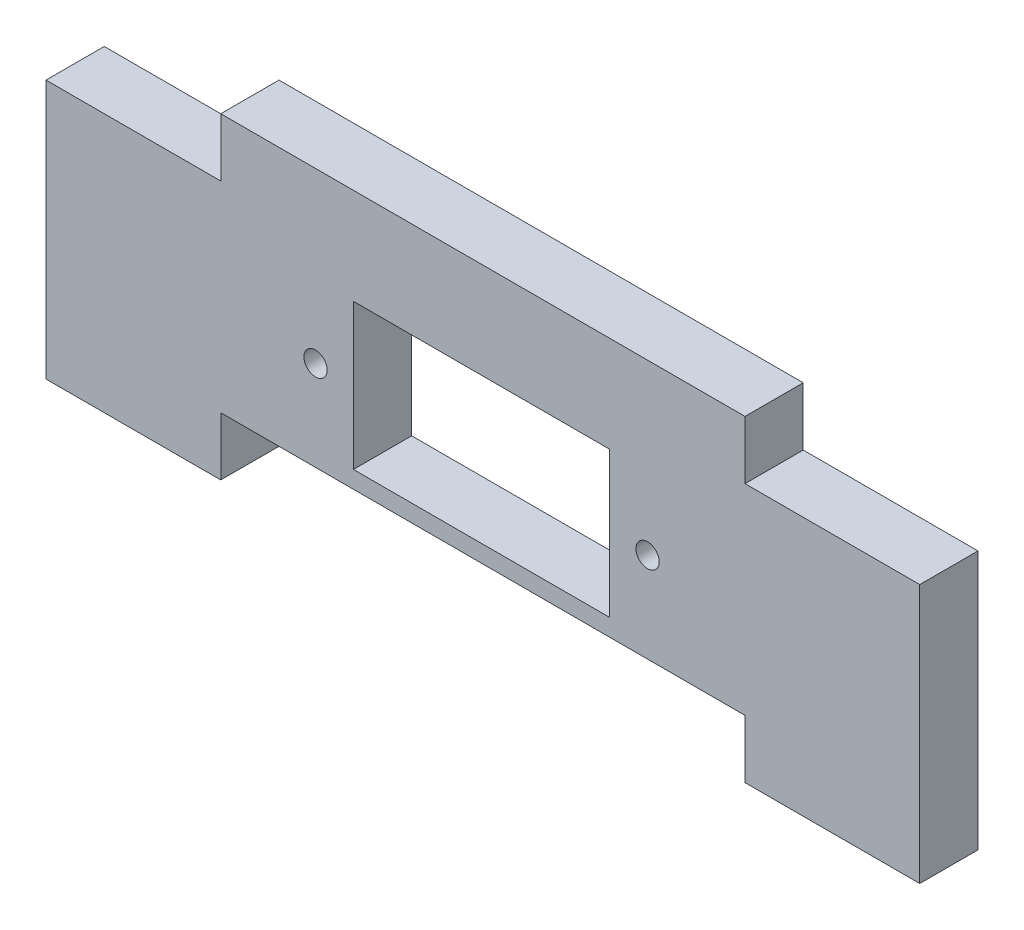
SolidWorks part; units mm, degrees
ref_plane "Front Plane" through (0, 0, 0) normal (0, 0, 1) x (1, 0, 0)
ref_plane "Top Plane" through (0, 0, 0) normal (0, 1, 0) x (1, 0, 0)
ref_plane "Right Plane" through (0, 0, 0) normal (1, 0, 0) x (0, 0, -1)
sketch "Sketch1" plane through (0, 0, 232.248) normal (0, 0, 1) x (1, 0, 0)
  line L0 (-82.2575, 116.9148) -> (-82.2575, 82.4648)
  line L1 (-82.2575, 82.4648) -> (-82.2575, 72.4648)
  line L2 (-29.4825, 110.4148) -> (14.5175, 110.4148)
  line L3 (-82.2575, 72.4648) -> (-52.2575, 72.4648)
  line L4 (-29.4825, 82.4648) -> (14.9675, 82.4648)
  line L5 (-52.2575, 72.4648) -> (-52.2575, 82.4648)
  line L6 (-29.4825, 85.4148) -> (14.5175, 85.4148)
  line L7 (-52.2575, 82.4648) -> (-29.4825, 82.4648)
  line L8 (-29.4825, 85.4148) -> (-29.4825, 110.4148)
  line L9 (-52.2575, 126.9148) -> (37.7425, 126.9148)
  line L11 (280.006, 122.4648) -> (-294.5209, 122.4648) construction
  line L12 (-29.4825, 116.9148) -> (14.9675, 116.9148) construction
  line L13 (-52.2575, 126.9148) -> (-52.2575, 116.9148)
  line L14 (-52.2575, 116.9148) -> (-82.2575, 116.9148)
  line L15 (37.7425, 82.4648) -> (14.9675, 82.4648)
  line L16 (-7.2575, 111.3889) -> (-7.2575, 148.6392) construction
  line L17 (-29.4825, 111.3889) -> (14.9675, 111.3889) construction
  line L18 (37.7425, 116.9148) -> (67.7425, 116.9148)
  line L19 (37.7425, 126.9148) -> (37.7425, 116.9148)
  line L20 (14.5175, 85.4148) -> (14.5175, 110.4148)
  line L21 (37.7425, 72.4648) -> (37.7425, 82.4648)
  line L22 (67.7425, 82.4648) -> (67.7425, 72.4648)
  line L23 (67.7425, 72.4648) -> (37.7425, 72.4648)
  line L26 (67.7425, 116.9148) -> (67.7425, 82.4648)
  line L27 (16.1124, 116.9148) -> (-30.6274, 116.9148) construction
  point P28 (-7.2575, 122.4648)
  point P32 (-7.2575, 116.9148)
  dimension "D1" = 30
  dimension "D2" = 10
  dimension "D3" = 45
  dimension "D4" = 10
  dimension "D5" = 6.5
  dimension "D6" = 44
  dimension "D7" = 25
  dimension "D8" = 44.45
extrude "Boss-Extrude1" add sketch "Sketch1" against normal blind 10
hole_wizard "Ø4.0 (4) Diameter Hole1" positions "Sketch2" profile "Sketch3" hole size "Ø4.0" standard "ANSI Metric"
sketch "Sketch2" plane through (-7.2575, 0, 222.248) normal (0, 0, -1) x (-1, 0, 0)
  point P0 (-28.275, 97.9148)
  point P3 (28.725, 97.9148)
sketch "Sketch3" plane through (21.0175, 97.9148, 222.248) normal (1, 0, 0) x (0, 1, 0)
  line L0 (0, 0) -> (0, 26.2017)
  line L1 (0, 26.2017) -> (2, 25)
  line L2 (2, 25) -> (2, 0)
  line L3 (2, 0) -> (0, 0)
  line L4 (0, 26.2017) -> (-2, 25) construction
  line L5 (0, -6.35) -> (0, 107.95) construction
  dimension "Hole Dia." = 4
  dimension "Hole Depth" = 25
  dimension "Drill Angle" = 118
